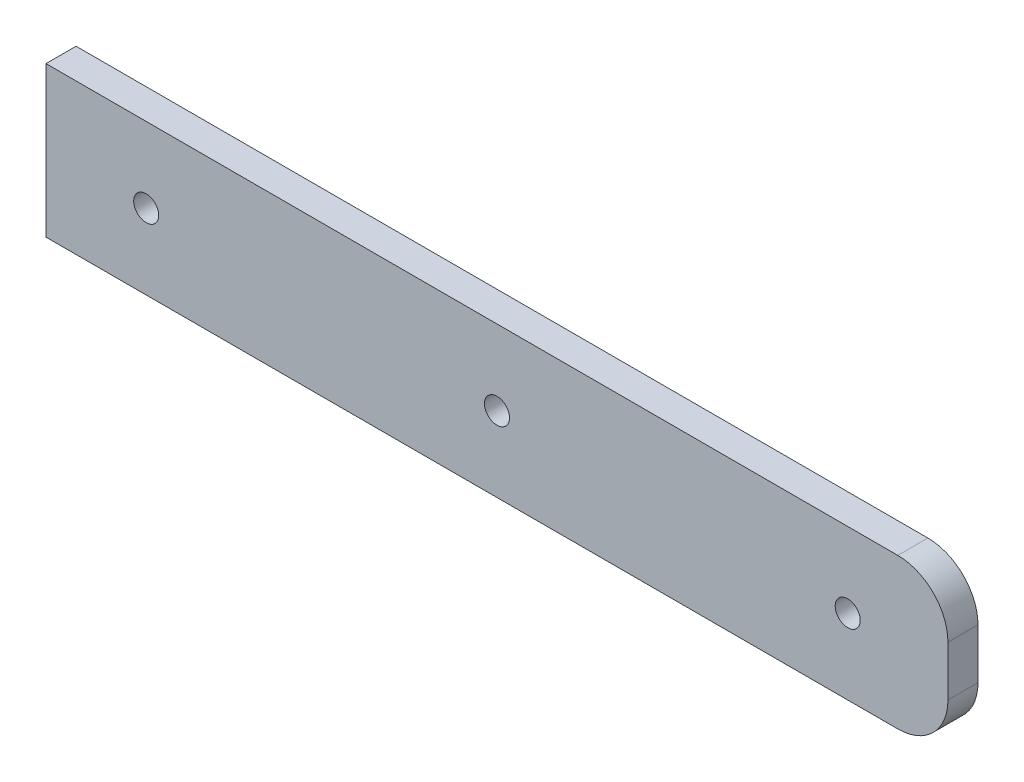
SolidWorks part; units mm, degrees
ref_plane "Front Plane" through (0, 0, 0) normal (0, 0, 1) x (1, 0, 0)
ref_plane "Top Plane" through (0, 0, 0) normal (0, 1, 0) x (1, 0, 0)
ref_plane "Right Plane" through (0, 0, 0) normal (1, 0, 0) x (0, 0, -1)
sketch "Sketch2" plane through (0, 0, 0) normal (0, 0, 1) x (1, 0, 0)
  line L0 (202.6774, 303.3286) -> (22.6774, 303.3286) construction
  line L5 (22.6774, 318.3286) -> (202.6774, 318.3286)
  line L6 (22.6774, 318.3286) -> (22.6774, 288.3286)
  line L7 (22.6774, 288.3286) -> (202.6774, 288.3286)
  line L17 (202.6774, 318.3286) -> (202.6774, 288.3286)
  circle A16 centre (182.6774, 303.3286) radius 2.5
  circle A17 centre (112.6774, 303.3286) radius 2.5
  circle A18 centre (42.6774, 303.3286) radius 2.5
  dimension "D4" = 20
  dimension "D3" = 5
  dimension "D1" = 180
  dimension "D2" = 30
  dimension "D5" = 3
extrude "Boss-Extrude1" add sketch "Sketch2" along normal blind 6 contours L17 L0 A16 A17 A18 L6 L7 | L0 L17 L5 L6 A18 A17 A16 region at (112.6774, 295.7576, 0) region at (112.6774, 310.8996, 0)
fillet "Fillet1" radius 10 2 edges at (202.6774, 288.3286, 3) (202.6774, 318.3286, 3)
